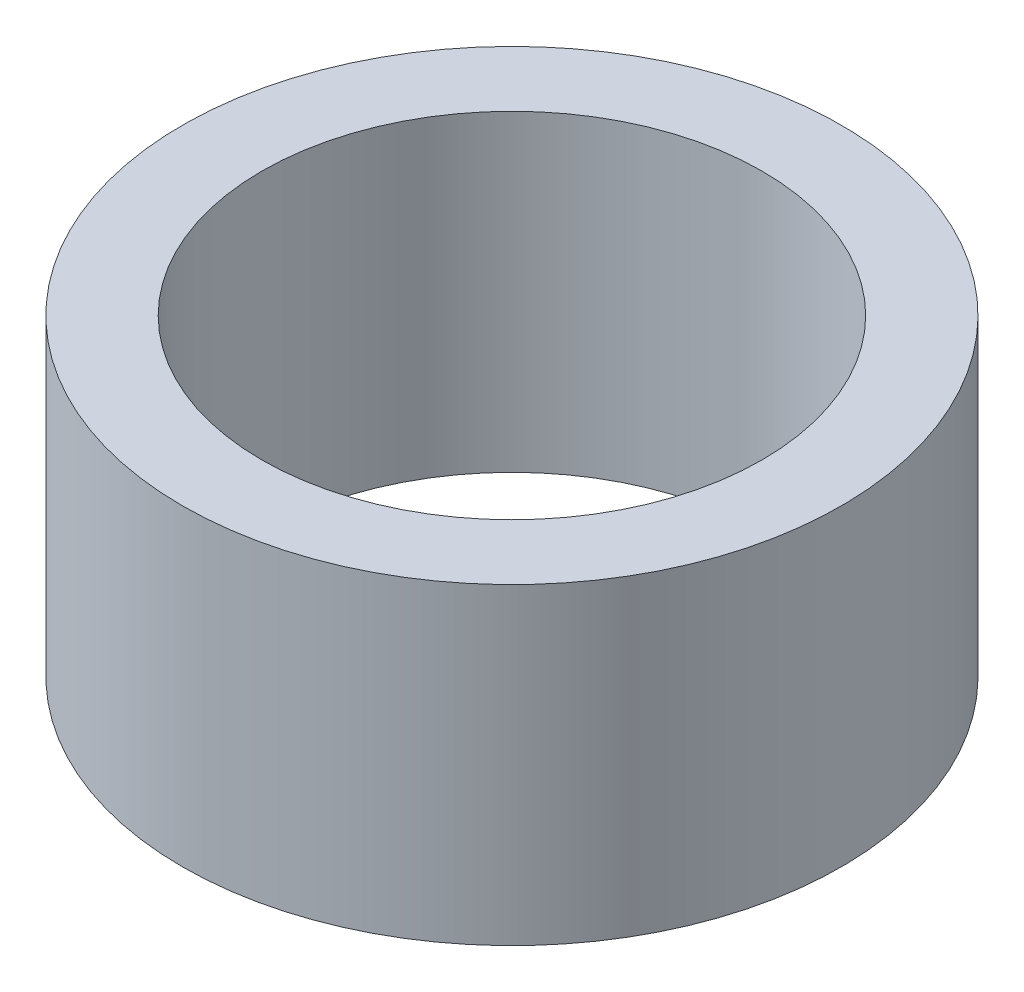
SolidWorks part; units mm, degrees
ref_plane "Front Plane" through (0, 0, 0) normal (0, 0, 1) x (1, 0, 0)
ref_plane "Top Plane" through (0, 0, 0) normal (0, 1, 0) x (1, 0, 0)
ref_plane "Right Plane" through (0, 0, 0) normal (1, 0, 0) x (0, 0, -1)
sketch "Sketch1" plane through (0, 0, 0) normal (0, 1, 0) x (1, 0, 0)
  circle A0 centre (0, 0) radius 4
  circle A1 centre (0, 0) radius 5.27
  dimension "8mm" = 8
  dimension "D2" = 1.27
extrude "Boss-Extrude1" add sketch "Sketch1" along normal blind 5
